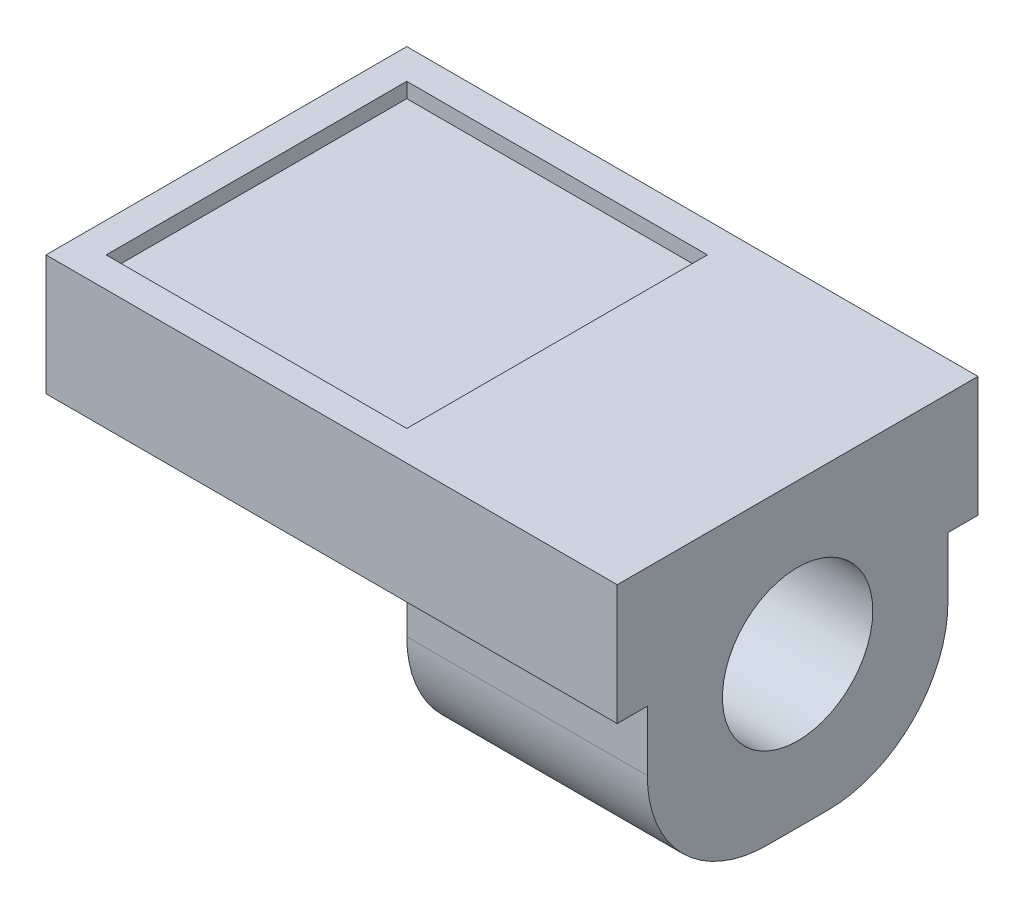
SolidWorks part; units mm, degrees
ref_plane "Front Plane" through (0, 0, 0) normal (0, 0, 1) x (1, 0, 0)
ref_plane "Top Plane" through (0, 0, 0) normal (0, 1, 0) x (1, 0, 0)
ref_plane "Right Plane" through (0, 0, 0) normal (1, 0, 0) x (0, 0, -1)
sketch "Sketch2" plane through (0, 0, 0) normal (0, 1, 0) x (1, 0, 0)
  line L1 (-4, -5) -> (4, -5)
  line L2 (-4, -5) -> (-4, 5)
  line L3 (-4, 5) -> (4, 5)
  line L4 (4, -5) -> (4, 5)
  line L5 (-4, -5) -> (4, 5) construction
  line L6 (-4, 5) -> (4, -5) construction
  point P0 (0, 0)
  dimension "D1" = 10
  dimension "D2" = 8
extrude "Boss-Extrude1" add sketch "Sketch2" along normal blind 8
sketch "Sketch4" plane through (0, 8, 0) normal (0, 1, 0) x (1, 0, 0)
  line L1 (4, -5) -> (-15, -5)
  line L2 (4, -5) -> (4, 5)
  line L3 (4, 5) -> (-15, 5)
  line L4 (-15, -5) -> (-15, 5)
  dimension "D1" = 19
extrude "Boss-Extrude2" add sketch "Sketch4" along normal blind 2
sketch "Sketch6" plane through (0, 0, 5) normal (0, 0, 1) x (1, 0, 0)
  line L1 (4, 10) -> (-15, 10)
  line L2 (4, 10) -> (4, 6)
  line L3 (4, 6) -> (-15, 6)
  line L4 (-15, 10) -> (-15, 6)
  point P5 (-16.1692, 10)
  point P6 (0, 0)
  point P7 (-16, 10)
  dimension "D1" = 4
extrude "Boss-Extrude3" add sketch "Sketch6" along normal blind 1
mirror "Mirror1" about plane through (0, 0, 0) normal (0, 0, 1) of "Boss-Extrude3"
sketch "Sketch7" plane through (0, 8, 0) normal (0, -1, 0) x (1, 0, 0)
  line L1 (-15, -5) -> (-14, -5)
  line L2 (-15, -5) -> (-15, 5)
  line L3 (-15, 5) -> (-14, 5)
  line L4 (-14, -5) -> (-14, 5)
  line L5 (-15, 5) -> (-4, 5) construction
  point P4 (0, 0)
  point P5 (-15, -5)
  dimension "D1" = 1
extrude "Boss-Extrude4" add sketch "Sketch7" along normal blind 2
sketch "Sketch3" plane through (4, 0, 0) normal (1, 0, 0) x (0, 0, -1)
  line L1 (-5, 0) -> (5, 0) construction
  circle A0 centre (0, 5) radius 2.5
  point P6 (0, 0)
  dimension "D1" = 5
  dimension "D2" = 5
extrude "Cut-Extrude1" cut sketch "Sketch3" against normal up to next
sketch "Sketch8" plane through (0, 0, 0) normal (0, -1, 0) x (1, 0, 0)
  circle A0 centre (0, 0) radius 1
  dimension "D1" = 2
extrude "Cut-Extrude2" cut sketch "Sketch8" against normal up to next
fillet "Fillet3" radius 4 2 edges at (0, 0, 5) (0, 0, -5)
sketch "Sketch9" plane through (0, 10, 0) normal (0, 1, 0) x (1, 0, 0)
  line L0 (-15, 6) -> (-15, -6) construction
  line L1 (-14, 5) -> (-4, 5)
  line L2 (-14, 5) -> (-14, -5)
  line L3 (-14, -5) -> (-4, -5)
  line L4 (-4, 5) -> (-4, -5)
  line L5 (-14, 5) -> (-4, -5) construction
  line L6 (-14, -5) -> (-4, 5) construction
  point P0 (-9, 0)
  point P7 (0, 0)
  dimension "D1" = 10
  dimension "D2" = 10
  dimension "D3" = 6
extrude "Cut-Extrude3" cut sketch "Sketch9" against normal blind 0.5 contours L2 L1 L4 L3
